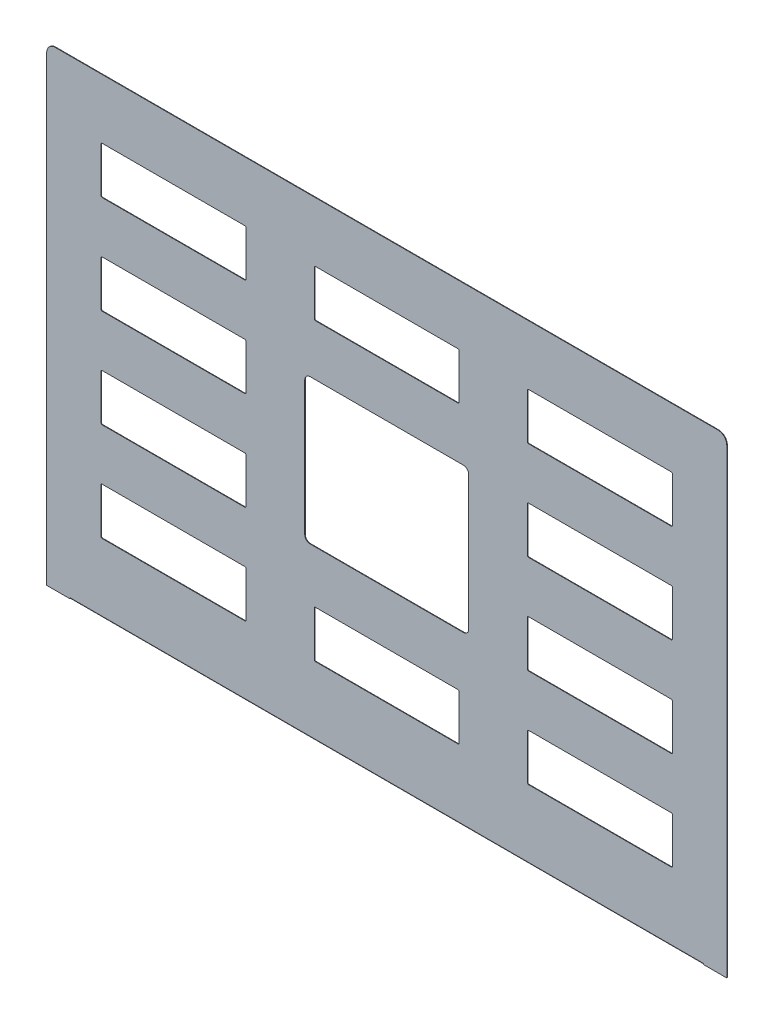
SolidWorks part; units mm, degrees
note: The reader was unsure of these and kept them because the rebuilt part matched: flange length of "Edge-Flange1".
ref_plane "Front Plane" through (0, 0, 0) normal (0, 0, 1) x (1, 0, 0)
ref_plane "Top Plane" through (0, 0, 0) normal (0, 1, 0) x (1, 0, 0)
ref_plane "Right Plane" through (0, 0, 0) normal (1, 0, 0) x (0, 0, -1)
sketch "Sketch1" plane through (0, 0, 0) normal (0, 0, 1) x (1, 0, 0)
  line L1 (0, 0) -> (1244, 0)
  line L2 (0, 0) -> (0, 844)
  line L3 (16, 860) -> (1228, 860)
  line L4 (1244, 0) -> (1244, 844)
  arc A0 (1228, 860) -> (1244, 844) centre (1228, 844) cw
  arc A1 (0, 844) -> (16, 860) centre (16, 844) cw
  dimension "D3" = 16
  dimension "D1" = 1244
  dimension "D2" = 860
base flange "Base-Flange1" sketch "Sketch1" thickness 1 reverse thickness direction no parameters "D1"=1
edge flange "Edge-Flange1" sketch "Sketch8" flange angle 90 flange length 18 flange position material inside bend radius 1 thickness 1 relief rectangular parameters "D6"=10
sketch "Sketch8" plane through (0, 0, -1) normal (0, -1, 0) x (-1, 0, 0)
  line L0 (0, 0) -> (-1244, 0) construction
  line L1 (-43, 0) -> (-1201, 0)
  line L2 (-1201, 0) -> (-1201, 18)
  line L3 (-1201, 18) -> (-43, 18)
  line L4 (-43, 18) -> (-43, 0)
  line L5 (0, 0) -> (0, -1) construction
  line L6 (-1244, 0) -> (-1244, -1) construction
  circle A0 centre (-82, 9) radius 2.75
  circle A1 centre (-262, 9) radius 2.75
  circle A2 centre (-442, 9) radius 2.75
  circle A3 centre (-622, 9) radius 2.75
  circle A4 centre (-802, 9) radius 2.75
  circle A5 centre (-982, 9) radius 2.75
  circle A6 centre (-1162, 9) radius 2.75
  point P6 (-43, 9)
  dimension "D1" = 5.5
  dimension "D2" = 39
  dimension "D4" = 43
  dimension "D5" = 43
  dimension "D3" = 7
bend "EdgeBend1" bend radius 1 bend angle 90 parameters "D5"=1
sketch "Sketch9" plane through (0, 0, 0) normal (0, 0, 1) x (1, 0, 0)
  line L0 (1244, 0) -> (1244, 844) construction
  line L1 (1142.5, 751) -> (881.5, 751)
  line L2 (1144.5, 749) -> (1144.5, 667)
  line L3 (1142.5, 665) -> (881.5, 665)
  line L4 (879.5, 749) -> (879.5, 667)
  line L5 (1228, 860) -> (16, 860) construction
  line L6 (754.5, 749) -> (754.5, 667)
  line L7 (752.5, 751) -> (491.5, 751)
  line L8 (752.5, 665) -> (491.5, 665)
  line L9 (489.5, 749) -> (489.5, 667)
  line L10 (364.5, 749) -> (364.5, 667)
  line L11 (362.5, 751) -> (101.5, 751)
  line L12 (362.5, 665) -> (101.5, 665)
  line L13 (99.5, 749) -> (99.5, 667)
  line L18 (364.5, 569) -> (364.5, 487)
  line L19 (362.5, 571) -> (101.5, 571)
  line L20 (362.5, 485) -> (101.5, 485)
  line L21 (99.5, 569) -> (99.5, 487)
  line L26 (364.5, 389) -> (364.5, 307)
  line L27 (362.5, 391) -> (101.5, 391)
  line L28 (362.5, 305) -> (101.5, 305)
  line L29 (99.5, 389) -> (99.5, 307)
  line L30 (754.5, 209) -> (754.5, 127)
  line L31 (752.5, 211) -> (491.5, 211)
  line L32 (752.5, 125) -> (491.5, 125)
  line L33 (489.5, 209) -> (489.5, 127)
  line L34 (364.5, 209) -> (364.5, 127)
  line L35 (362.5, 211) -> (101.5, 211)
  line L36 (362.5, 125) -> (101.5, 125)
  line L37 (99.5, 209) -> (99.5, 127)
  line L38 (1144.5, 569) -> (1144.5, 487)
  line L39 (1142.5, 571) -> (881.5, 571)
  line L40 (1142.5, 485) -> (881.5, 485)
  line L41 (879.5, 569) -> (879.5, 487)
  line L42 (1144.5, 389) -> (1144.5, 307)
  line L43 (1142.5, 391) -> (881.5, 391)
  line L44 (1142.5, 305) -> (881.5, 305)
  line L45 (879.5, 389) -> (879.5, 307)
  line L46 (1144.5, 209) -> (1144.5, 127)
  line L47 (1142.5, 211) -> (881.5, 211)
  line L48 (1142.5, 125) -> (881.5, 125)
  line L49 (879.5, 209) -> (879.5, 127)
  line L50 (754.5, 389) -> (754.5, 307) [skipped]
  line L51 (754.5, 569) -> (754.5, 487) [skipped]
  line L52 (752.5, 571) -> (491.5, 571) [skipped]
  line L53 (752.5, 485) -> (491.5, 485) [skipped]
  line L54 (489.5, 569) -> (489.5, 487) [skipped]
  line L55 (752.5, 391) -> (491.5, 391) [skipped]
  line L56 (752.5, 305) -> (491.5, 305) [skipped]
  line L57 (489.5, 389) -> (489.5, 307) [skipped]
  arc A0 (1144.5, 667) -> (1142.5, 665) centre (1142.5, 667) cw
  arc A1 (881.5, 665) -> (879.5, 667) centre (881.5, 667) cw
  arc A2 (881.5, 751) -> (879.5, 749) centre (881.5, 749) ccw
  arc A3 (1142.5, 751) -> (1144.5, 749) centre (1142.5, 749) cw
  arc A4 (752.5, 751) -> (754.5, 749) centre (752.5, 749) cw
  arc A5 (754.5, 667) -> (752.5, 665) centre (752.5, 667) cw
  arc A6 (491.5, 665) -> (489.5, 667) centre (491.5, 667) cw
  arc A7 (491.5, 751) -> (489.5, 749) centre (491.5, 749) ccw
  arc A8 (362.5, 751) -> (364.5, 749) centre (362.5, 749) cw
  arc A9 (364.5, 667) -> (362.5, 665) centre (362.5, 667) cw
  arc A10 (101.5, 665) -> (99.5, 667) centre (101.5, 667) cw
  arc A11 (101.5, 751) -> (99.5, 749) centre (101.5, 749) ccw
  arc A16 (362.5, 571) -> (364.5, 569) centre (362.5, 569) cw
  arc A17 (364.5, 487) -> (362.5, 485) centre (362.5, 487) cw
  arc A18 (101.5, 485) -> (99.5, 487) centre (101.5, 487) cw
  arc A19 (101.5, 571) -> (99.5, 569) centre (101.5, 569) ccw
  arc A24 (362.5, 391) -> (364.5, 389) centre (362.5, 389) cw
  arc A25 (364.5, 307) -> (362.5, 305) centre (362.5, 307) cw
  arc A26 (101.5, 305) -> (99.5, 307) centre (101.5, 307) cw
  arc A27 (101.5, 391) -> (99.5, 389) centre (101.5, 389) ccw
  arc A28 (752.5, 211) -> (754.5, 209) centre (752.5, 209) cw
  arc A29 (754.5, 127) -> (752.5, 125) centre (752.5, 127) cw
  arc A30 (491.5, 125) -> (489.5, 127) centre (491.5, 127) cw
  arc A31 (491.5, 211) -> (489.5, 209) centre (491.5, 209) ccw
  arc A32 (362.5, 211) -> (364.5, 209) centre (362.5, 209) cw
  arc A33 (364.5, 127) -> (362.5, 125) centre (362.5, 127) cw
  arc A34 (101.5, 125) -> (99.5, 127) centre (101.5, 127) cw
  arc A35 (101.5, 211) -> (99.5, 209) centre (101.5, 209) ccw
  arc A36 (1142.5, 571) -> (1144.5, 569) centre (1142.5, 569) cw
  arc A37 (1144.5, 487) -> (1142.5, 485) centre (1142.5, 487) cw
  arc A38 (881.5, 485) -> (879.5, 487) centre (881.5, 487) cw
  arc A39 (881.5, 571) -> (879.5, 569) centre (881.5, 569) ccw
  arc A40 (1142.5, 391) -> (1144.5, 389) centre (1142.5, 389) cw
  arc A41 (1144.5, 307) -> (1142.5, 305) centre (1142.5, 307) cw
  arc A42 (881.5, 305) -> (879.5, 307) centre (881.5, 307) cw
  arc A43 (881.5, 391) -> (879.5, 389) centre (881.5, 389) ccw
  arc A44 (1142.5, 211) -> (1144.5, 209) centre (1142.5, 209) cw
  arc A45 (1144.5, 127) -> (1142.5, 125) centre (1142.5, 127) cw
  arc A46 (881.5, 125) -> (879.5, 127) centre (881.5, 127) cw
  arc A47 (881.5, 211) -> (879.5, 209) centre (881.5, 209) ccw
  arc A48 (754.5, 487) -> (752.5, 485) centre (752.5, 487) cw [skipped]
  arc A49 (491.5, 485) -> (489.5, 487) centre (491.5, 487) cw [skipped]
  arc A50 (752.5, 391) -> (754.5, 389) centre (752.5, 389) cw [skipped]
  arc A51 (754.5, 307) -> (752.5, 305) centre (752.5, 307) cw [skipped]
  arc A52 (491.5, 305) -> (489.5, 307) centre (491.5, 307) cw [skipped]
  arc A53 (491.5, 391) -> (489.5, 389) centre (491.5, 389) ccw [skipped]
  arc A54 (752.5, 571) -> (754.5, 569) centre (752.5, 569) cw [skipped]
  arc A55 (491.5, 571) -> (489.5, 569) centre (491.5, 569) ccw [skipped]
  dimension "D5" = 2
  dimension "D1" = 99.5
  dimension "D2" = 265
  dimension "D3" = 86
  dimension "D4" = 109
  dimension "D6" = 3
  dimension "D7" = 4
extrude "Cut-Extrude1" cut sketch "Sketch9" against normal blind 10 normal cut yes
sketch "Sketch10" plane through (0, 0, 0) normal (0, 0, 1) x (1, 0, 0)
  line L1 (482, 306.5) -> (762, 306.5)
  line L2 (472, 316.5) -> (472, 561.5)
  line L3 (482, 571.5) -> (762, 571.5)
  line L4 (772, 316.5) -> (772, 561.5)
  line L6 (1244, 0) -> (1244, 844) construction
  line L8 (1228, 860) -> (16, 860) construction
  arc A0 (482, 306.5) -> (472, 316.5) centre (482, 316.5) cw
  arc A1 (762, 306.5) -> (772, 316.5) centre (762, 316.5) ccw
  arc A2 (472, 561.5) -> (482, 571.5) centre (482, 561.5) cw
  arc A3 (762, 571.5) -> (772, 561.5) centre (762, 561.5) cw
  dimension "D5" = 10
  dimension "D1" = 300
  dimension "D2" = 265
  dimension "D3" = 288.5
  dimension "D4" = 472
extrude "Cut-Extrude2" cut sketch "Sketch10" against normal blind 10 normal cut yes
sketch "Sketch11" plane through (0, 0, -1) normal (0, 0, -1) x (-1, 0, 0)
  line L0 (-764.7929, 589.1928) -> (-479.2071, 589.1928) construction
  line L1 (-454, 564.3403) -> (-454, 309.3) construction
  line L2 (-479.2071, 283.7739) -> (-764.7929, 283.7739) construction
  line L3 (-790, 564.3403) -> (-790, 309.3) construction
  line L4 (-460.5, 511.3403) -> (-443.4779, 511.3403) construction
  line L5 (-460.5, 362.3) -> (-447.3951, 362.3) construction
  line L6 (-511.2071, 290.2739) -> (-511.2071, 278.9845) construction
  line L7 (-621.9571, 290.2739) -> (-621.9571, 277.299) construction
  line L8 (-732.7071, 290.2739) -> (-732.7071, 278.5303) construction
  line L9 (-783.5, 362.3) -> (-796.1053, 362.3) construction
  line L10 (-783.5, 511.3403) -> (-798.0884, 511.3403) construction
  line L11 (-732.7071, 584.2906) -> (-732.7071, 593.6234) construction
  line L12 (-622, 584.2906) -> (-622, 595.0309) construction
  line L13 (-511.2929, 582.8038) -> (-511.2929, 595.7777) construction
  arc A0 (-479.2071, 283.7739) -> (-476.2071, 286.7739) centre (-479.2071, 286.7739) ccw construction
  arc A1 (-454, 517.3195) -> (-454, 505.3612) centre (-454.5, 511.3403) ccw construction
  arc A2 (-454, 368.2791) -> (-454, 356.3209) centre (-454.5, 362.3) ccw construction
  arc A3 (-505.228, 283.7739) -> (-517.1862, 283.7739) centre (-511.2071, 284.2739) ccw construction
  arc A4 (-615.978, 283.7739) -> (-627.9362, 283.7739) centre (-621.9571, 284.2739) ccw construction
  arc A5 (-726.728, 283.7739) -> (-738.6862, 283.7739) centre (-732.7071, 284.2739) ccw construction
  arc A6 (-790, 356.3209) -> (-790, 368.2791) centre (-789.5, 362.3) ccw construction
  arc A7 (-790, 505.3612) -> (-790, 517.3195) centre (-789.5, 511.3403) ccw construction
  ellipse E0 centre (-511.2929, 588.7014) end of major axis (-517.2929, 588.7014) minor radius 5.8976 (-517.272, 589.1928) -> (-505.3138, 589.1928) ccw construction
sketch "Bend-Lines1" [suppressed] plane through (0, 0, 0) normal (0, 1, 0) x (1, 0, 0)
sketch "Bounding-Box1" [suppressed] plane through (0, 0, 0) normal (0, 1, 0) x (1, 0, 0)
sheet metal parameters "Sheet-Metal1" thickness 1 parameters "D1"=2
flat pattern "Flat-Pattern1" [suppressed]
sketch "Bend-Lines2" plane through (0, 0, 0) normal (0, 1, 0) x (1, 0, 0)
sketch3d "Bounding-Box2" [suppressed]
  line L0 (15, 15, 0) -> (-1227, 15, 0) construction
  line L1 (15, -935, 0) -> (-1227, -935, 0) construction
  line L2 (15, 15, 0) -> (15, -935, 0) construction
  line L3 (-1227, 15, 0) -> (-1227, -935, 0) construction
sheet metal parameters "Sheet-Metal2" thickness 1 parameters "D1"=2
flat pattern "Flat-Pattern1"
sketch "Bend-Lines2" plane through (0, 0, 0) normal (0, 0, 1) x (1, 0, 0)
  line L0 (0, 0.8219) -> (1242, 0.8219) construction
  line L1 (0, 0.8219) -> (1242, 0.8219) construction
sketch3d "Bounding-Box2" [suppressed]
  line L0 (-15, 15, 0) -> (1227, 15, 0) construction
  line L1 (-15, -946.3562, 0) -> (1227, -946.3562, 0) construction
  line L2 (-15, 15, 0) -> (-15, -946.3562, 0) construction
  line L3 (1227, 15, 0) -> (1227, -946.3562, 0) construction
bend of the flat pattern "Flatten-<EdgeBend1>1"
sheet metal parameters "Sheet-Metal3" thickness 1 parameters "D1"=2
flat pattern "Flat-Pattern1"
sketch "Bend-Lines2" plane through (0, 0, 0) normal (0, 0, 1) x (1, 0, 0)
  line L0 (0, 0.8219) -> (1244, 0.8219) construction
  line L1 (0, 0.8219) -> (1244, 0.8219) construction
sketch3d "Bounding-Box2" [suppressed]
  line L0 (-16, 16, 0) -> (1228, 16, 0) construction
  line L1 (-16, -945.3562, 0) -> (1228, -945.3562, 0) construction
  line L2 (-16, 16, 0) -> (-16, -945.3562, 0) construction
  line L3 (1228, 16, 0) -> (1228, -945.3562, 0) construction
bend of the flat pattern "Flatten-<EdgeBend1>1"
sheet metal parameters "Sheet-Metal4" thickness 1 parameters "D1"=2
flat pattern "Flat-Pattern1"
sketch "Bend-Lines2" plane through (0, 0, 0) normal (0, 0, 1) x (1, 0, 0)
  line L0 (43, 0.8219) -> (1201, 0.8219) construction
  line L1 (43, 0.8219) -> (1201, 0.8219) construction
sketch3d "Bounding-Box2" [suppressed]
  line L0 (-16, 16, 0) -> (1228, 16, 0) construction
  line L1 (-16, -861.3562, 0) -> (1228, -861.3562, 0) construction
  line L2 (-16, 16, 0) -> (-16, -861.3562, 0) construction
  line L3 (1228, 16, 0) -> (1228, -861.3562, 0) construction
bend of the flat pattern "Flatten-<EdgeBend1>1"
equation "\"D5@Sketch8\"=\"D4@Sketch8\""
